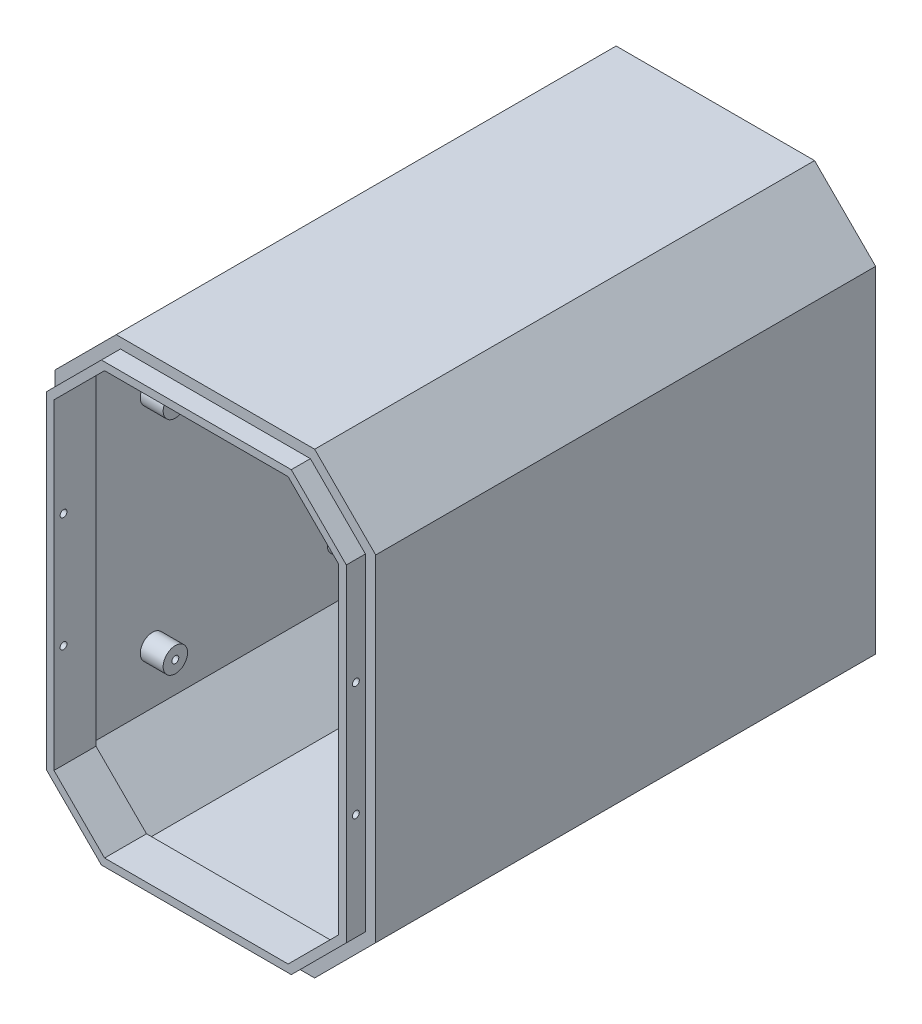
SolidWorks part; units mm, degrees
ref_plane "Front Plane" through (0, 0, 0) normal (0, 0, 1) x (1, 0, 0)
ref_plane "Top Plane" through (0, 0, 0) normal (0, 1, 0) x (1, 0, 0)
ref_plane "Right Plane" through (0, 0, 0) normal (1, 0, 0) x (0, 0, -1)
ref_plane "PZ_p37_000" through (0, 0, 37) normal (0, 0, 1) x (1, 0, 0)
sketch "S_prism1" plane through (0, 0, 37) normal (0, 0, 1) x (1, 0, 0)
  line L0 (42, -44) -> (42, 44)
  line L1 (42, 44) -> (26, 60)
  line L2 (26, 60) -> (-26, 60)
  line L3 (-26, 60) -> (-42, 44)
  line L4 (-42, 44) -> (-42, -44)
  line L5 (-42, -44) -> (-26, -60)
  line L6 (-26, -60) -> (26, -60)
  line L7 (26, -60) -> (42, -44)
extrude "Boss_1" add sketch "S_prism1" along normal blind 131
ref_plane "PZ_p71_425" through (0, 0, 71.425) normal (0, 0, 1) x (1, 0, 0)
sketch "S_pcut2" plane through (0, 0, 71.425) normal (0, 0, 1) x (1, 0, 0)
  line L0 (39.5, -42.9645) -> (39.5, 42.9645)
  line L1 (39.5, 42.9645) -> (24.9645, 57.5)
  line L2 (24.9645, 57.5) -> (-24.9645, 57.5)
  line L3 (-24.9645, 57.5) -> (-39.5, 42.9645)
  line L4 (-39.5, 42.9645) -> (-39.5, -42.9645)
  line L5 (-39.5, -42.9645) -> (-24.9645, -57.5)
  line L6 (-24.9645, -57.5) -> (24.9645, -57.5)
  line L7 (24.9645, -57.5) -> (39.5, -42.9645)
extrude "Cut_2" cut sketch "S_pcut2" along normal blind 96.675
ref_plane "PZ_p36_900" through (0, 0, 36.9) normal (0, 0, 1) x (1, 0, 0)
sketch "S_pcut3" plane through (0, 0, 36.9) normal (0, 0, 1) x (1, 0, 0)
  line L0 (39.5, -42.9645) -> (39.5, 42.9645)
  line L1 (39.5, 42.9645) -> (24.9645, 57.5)
  line L2 (24.9645, 57.5) -> (-24.9645, 57.5)
  line L3 (-24.9645, 57.5) -> (-39.5, 42.9645)
  line L4 (-39.5, 42.9645) -> (-39.5, -42.9645)
  line L5 (-39.5, -42.9645) -> (-24.9645, -57.5)
  line L6 (-24.9645, -57.5) -> (24.9645, -57.5)
  line L7 (24.9645, -57.5) -> (39.5, -42.9645)
extrude "Cut_3" cut sketch "S_pcut3" along normal blind 32.025
ref_plane "PZ_p68_825" through (0, 0, 68.825) normal (0, 0, 1) x (1, 0, 0)
sketch "S_cut4" plane through (0, 0, 68.825) normal (0, 0, 1) x (1, 0, 0)
  line L0 (-34, -14) -> (-26, -14)
  line L1 (-26, -14) -> (-26, 14)
  line L2 (-26, 14) -> (-34, 14)
  line L3 (-34, 14) -> (-34, -14)
  dimension "P1" = 34
  dimension "P2" = 14
  dimension "P3" = 26
  dimension "P4" = 14
  dimension "P5" = 26
  dimension "P6" = 14
  dimension "P7" = 34
  dimension "P8" = 14
extrude "Pocket_4" cut sketch "S_cut4" along normal blind 2.7
ref_plane "PX_m42_100" through (-42.1, 0, 0) normal (1, 0, 0) x (0, 0, -1)
sketch "S_hole5" plane through (-42.1, 0, 0) normal (1, 0, 0) x (0, 0, -1)
  circle A0 centre (-88, 0) radius 6
  dimension "D1_S_hole5" = 12
  dimension "P2" = 88
extrude "Hole_5" cut sketch "S_hole5" along normal blind 2.7
sketch "S_cut6" plane through (0, 0, 68.825) normal (0, 0, 1) x (1, 0, 0)
  line L0 (-9.7, 27.8) -> (9.7, 27.8)
  line L1 (9.7, 27.8) -> (9.7, 34.1)
  line L2 (9.7, 34.1) -> (-9.7, 34.1)
  line L3 (-9.7, 34.1) -> (-9.7, 27.8)
  dimension "P1" = 9.7
  dimension "P2" = 27.8
  dimension "P3" = 9.7
  dimension "P4" = 27.8
  dimension "P5" = 9.7
  dimension "P6" = 34.1
  dimension "P7" = 9.7
  dimension "P8" = 34.1
extrude "Pocket_6" cut sketch "S_cut6" along normal blind 2.7
sketch "S_cut7" plane through (0, 0, 68.825) normal (0, 0, 1) x (1, 0, 0)
  line L0 (-9.7, -34.1) -> (9.7, -34.1)
  line L1 (9.7, -34.1) -> (9.7, -27.8)
  line L2 (9.7, -27.8) -> (-9.7, -27.8)
  line L3 (-9.7, -27.8) -> (-9.7, -34.1)
  dimension "P1" = 9.7
  dimension "P2" = 34.1
  dimension "P3" = 9.7
  dimension "P4" = 34.1
  dimension "P5" = 9.7
  dimension "P6" = 27.8
  dimension "P7" = 9.7
  dimension "P8" = 27.8
extrude "Pocket_7" cut sketch "S_cut7" along normal blind 2.7
sketch "S_hole8" plane through (0, 0, 68.825) normal (0, 0, 1) x (1, 0, 0)
  circle A0 centre (-20, -25) radius 1.7
  dimension "D1_S_hole8" = 3.4
  dimension "P2" = 20
  dimension "P3" = 25
extrude "Hole_8" cut sketch "S_hole8" along normal blind 2.7
sketch "S_hole9" plane through (0, 0, 68.825) normal (0, 0, 1) x (1, 0, 0)
  circle A0 centre (-20, 25) radius 1.7
  dimension "D1_S_hole9" = 3.4
  dimension "P2" = 20
  dimension "P3" = 25
extrude "Hole_9" cut sketch "S_hole9" along normal blind 2.7
sketch "S_hole10" plane through (0, 0, 68.825) normal (0, 0, 1) x (1, 0, 0)
  circle A0 centre (24, -25) radius 1.7
  dimension "D1_S_hole10" = 3.4
  dimension "P2" = 24
  dimension "P3" = 25
extrude "Hole_10" cut sketch "S_hole10" along normal blind 2.7
sketch "S_hole11" plane through (0, 0, 68.825) normal (0, 0, 1) x (1, 0, 0)
  circle A0 centre (24, 25) radius 1.7
  dimension "D1_S_hole11" = 3.4
  dimension "P2" = 24
  dimension "P3" = 25
extrude "Hole_11" cut sketch "S_hole11" along normal blind 2.7
ref_plane "PZ_p162_000" through (0, 0, 162) normal (0, 0, 1) x (1, 0, 0)
sketch "S_prism12" plane through (0, 0, 162) normal (0, 0, 1) x (1, 0, 0)
  line L0 (40, -43.1716) -> (40, 43.1716)
  line L1 (40, 43.1716) -> (25.1716, 58)
  line L2 (25.1716, 58) -> (-25.1716, 58)
  line L3 (-25.1716, 58) -> (-40, 43.1716)
  line L4 (-40, 43.1716) -> (-40, -43.1716)
  line L5 (-40, -43.1716) -> (-25.1716, -58)
  line L6 (-25.1716, -58) -> (25.1716, -58)
  line L7 (25.1716, -58) -> (40, -43.1716)
extrude "Boss_12" add sketch "S_prism12" along normal blind 6
ref_plane "PZ_p167_900" through (0, 0, 167.9) normal (0, 0, 1) x (1, 0, 0)
sketch "S_prism13" plane through (0, 0, 167.9) normal (0, 0, 1) x (1, 0, 0)
  line L0 (39.3, -42.8816) -> (39.3, 42.8816)
  line L1 (39.3, 42.8816) -> (24.8816, 57.3)
  line L2 (24.8816, 57.3) -> (-24.8816, 57.3)
  line L3 (-24.8816, 57.3) -> (-39.3, 42.8816)
  line L4 (-39.3, 42.8816) -> (-39.3, -42.8816)
  line L5 (-39.3, -42.8816) -> (-24.8816, -57.3)
  line L6 (-24.8816, -57.3) -> (24.8816, -57.3)
  line L7 (24.8816, -57.3) -> (39.3, -42.8816)
extrude "Boss_13" add sketch "S_prism13" along normal blind 5.1
ref_plane "PX_m40_000" through (-40, 0, 0) normal (1, 0, 0) x (0, 0, -1)
sketch "S_cyl14" plane through (-40, 0, 0) normal (1, 0, 0) x (0, 0, -1)
  circle A0 centre (-96, -29) radius 3.2
  dimension "D1_S_cyl14" = 6.4
  dimension "P2" = 96
  dimension "P3" = 29
extrude "Boss_14" add sketch "S_cyl14" along normal blind 6.5
sketch "S_cyl15" plane through (-40, 0, 0) normal (1, 0, 0) x (0, 0, -1)
  circle A0 centre (-145, -29) radius 3.2
  dimension "D1_S_cyl15" = 6.4
  dimension "P2" = 145
  dimension "P3" = 29
extrude "Boss_15" add sketch "S_cyl15" along normal blind 6.5
sketch "S_cyl16" plane through (-40, 0, 0) normal (1, 0, 0) x (0, 0, -1)
  circle A0 centre (-96, 29) radius 3.2
  dimension "D1_S_cyl16" = 6.4
  dimension "P2" = 96
  dimension "P3" = 29
extrude "Boss_16" add sketch "S_cyl16" along normal blind 6.5
sketch "S_cyl17" plane through (-40, 0, 0) normal (1, 0, 0) x (0, 0, -1)
  circle A0 centre (-145, 29) radius 3.2
  dimension "D1_S_cyl17" = 6.4
  dimension "P2" = 145
  dimension "P3" = 29
extrude "Boss_17" add sketch "S_cyl17" along normal blind 6.5
ref_plane "PZ_p161_900" through (0, 0, 161.9) normal (0, 0, 1) x (1, 0, 0)
sketch "S_pcut18" plane through (0, 0, 161.9) normal (0, 0, 1) x (1, 0, 0)
  line L0 (37.3, -42.0532) -> (37.3, 42.0532)
  line L1 (37.3, 42.0532) -> (24.0532, 55.3)
  line L2 (24.0532, 55.3) -> (-24.0532, 55.3)
  line L3 (-24.0532, 55.3) -> (-37.3, 42.0532)
  line L4 (-37.3, 42.0532) -> (-37.3, -42.0532)
  line L5 (-37.3, -42.0532) -> (-24.0532, -55.3)
  line L6 (-24.0532, -55.3) -> (24.0532, -55.3)
  line L7 (24.0532, -55.3) -> (37.3, -42.0532)
extrude "Cut_18" cut sketch "S_pcut18" along normal blind 11.2
ref_plane "PX_p37_100" through (37.1, 0, 0) normal (1, 0, 0) x (0, 0, -1)
sketch "S_hole19" plane through (37.1, 0, 0) normal (1, 0, 0) x (0, 0, -1)
  circle A0 centre (-170.5, -15) radius 0.9
  dimension "D1_S_hole19" = 1.8
  dimension "P2" = 170.5
  dimension "P3" = 15
extrude "Hole_19" cut sketch "S_hole19" along normal blind 2.7
sketch "S_hole20" plane through (37.1, 0, 0) normal (1, 0, 0) x (0, 0, -1)
  circle A0 centre (-170.5, 15) radius 0.9
  dimension "D1_S_hole20" = 1.8
  dimension "P2" = 170.5
  dimension "P3" = 15
extrude "Hole_20" cut sketch "S_hole20" along normal blind 2.7
ref_plane "PX_m39_800" through (-39.8, 0, 0) normal (1, 0, 0) x (0, 0, -1)
sketch "S_hole21" plane through (-39.8, 0, 0) normal (1, 0, 0) x (0, 0, -1)
  circle A0 centre (-170.5, -15) radius 0.9
  dimension "D1_S_hole21" = 1.8
  dimension "P2" = 170.5
  dimension "P3" = 15
extrude "Hole_21" cut sketch "S_hole21" along normal blind 2.7
sketch "S_hole22" plane through (-39.8, 0, 0) normal (1, 0, 0) x (0, 0, -1)
  circle A0 centre (-170.5, 15) radius 0.9
  dimension "D1_S_hole22" = 1.8
  dimension "P2" = 170.5
  dimension "P3" = 15
extrude "Hole_22" cut sketch "S_hole22" along normal blind 2.7
ref_plane "PX_m40_600" through (-40.6, 0, 0) normal (1, 0, 0) x (0, 0, -1)
sketch "S_hole23" plane through (-40.6, 0, 0) normal (1, 0, 0) x (0, 0, -1)
  circle A0 centre (-96, -29) radius 0.9
  dimension "D1_S_hole23" = 1.8
  dimension "P2" = 96
  dimension "P3" = 29
extrude "Hole_23" cut sketch "S_hole23" along normal blind 7.2
sketch "S_hole24" plane through (-40.6, 0, 0) normal (1, 0, 0) x (0, 0, -1)
  circle A0 centre (-145, -29) radius 0.9
  dimension "D1_S_hole24" = 1.8
  dimension "P2" = 145
  dimension "P3" = 29
extrude "Hole_24" cut sketch "S_hole24" along normal blind 7.2
sketch "S_hole25" plane through (-40.6, 0, 0) normal (1, 0, 0) x (0, 0, -1)
  circle A0 centre (-96, 29) radius 0.9
  dimension "D1_S_hole25" = 1.8
  dimension "P2" = 96
  dimension "P3" = 29
extrude "Hole_25" cut sketch "S_hole25" along normal blind 7.2
sketch "S_hole26" plane through (-40.6, 0, 0) normal (1, 0, 0) x (0, 0, -1)
  circle A0 centre (-145, 29) radius 0.9
  dimension "D1_S_hole26" = 1.8
  dimension "P2" = 145
  dimension "P3" = 29
extrude "Hole_26" cut sketch "S_hole26" along normal blind 7.2
equation "\"plate_t\" = 3"
equation "\"clearance\" = 0.5"
